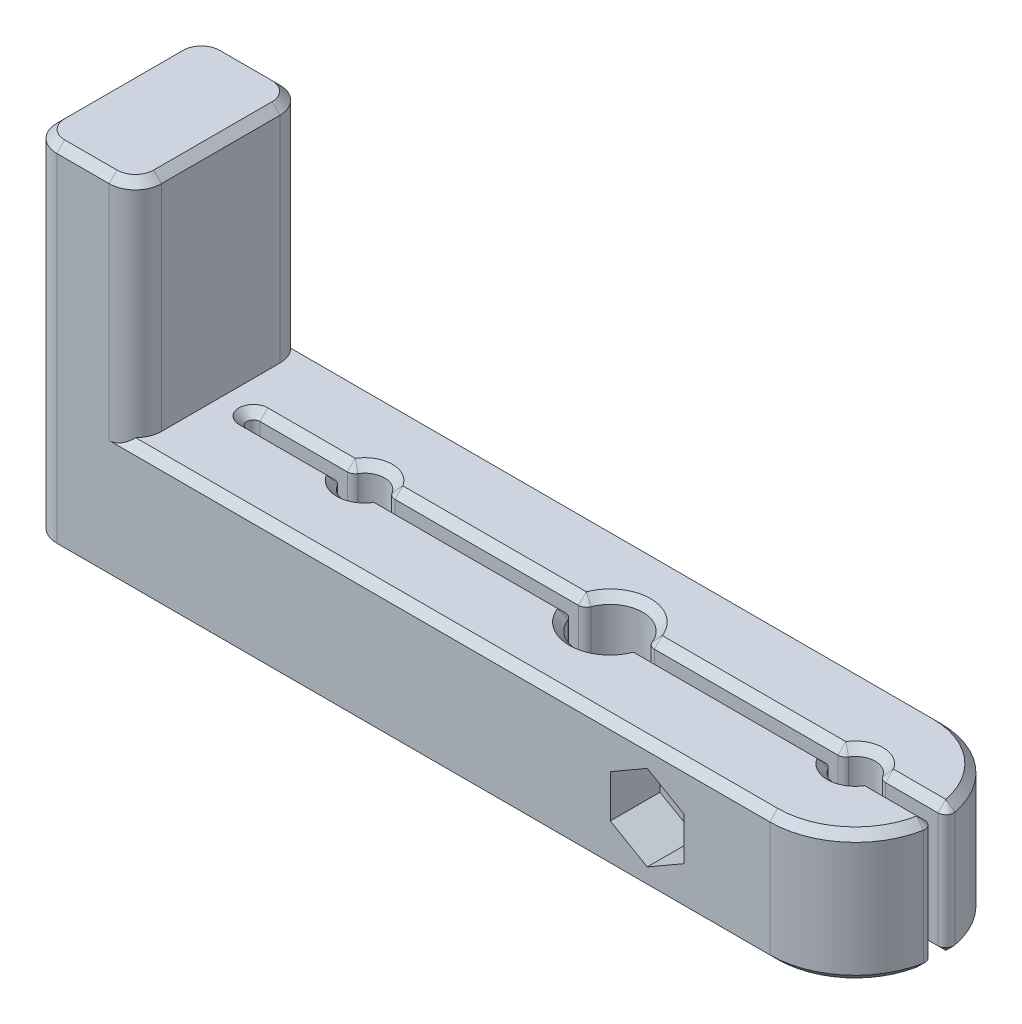
SolidWorks part; units mm, degrees
note: The reader was unsure of these and kept them because the rebuilt part matched: shared geometry of "Sketch1<4>", "Sketch3<3>".
ref_plane "Front Plane" through (0, 0, 0) normal (0, 0, 1) x (1, 0, 0)
ref_plane "Top Plane" through (0, 0, 0) normal (0, 1, 0) x (1, 0, 0)
ref_plane "Right Plane" through (0, 0, 0) normal (1, 0, 0) x (0, 0, -1)
sketch "Sketch1" plane through (0, 0, 0) normal (0, 1, 0) x (1, 0, 0)
  line L0 (0, 0) -> (-26.8494, 0) construction
  line L1 (0, 0) -> (0, 8.3452) construction
  line L2 (-18.75, 6.525) -> (18.75, 6.525)
  line L3 (-18.75, -6.525) -> (18.75, -6.525)
  line L4 (-18.75, 6.525) -> (-18.75, -6.525) construction
  line L5 (-18.75, 6.525) -> (-35.75, 6.525)
  line L6 (-37.75, 4.525) -> (-37.75, -4.525)
  line L7 (-35.75, -6.525) -> (-18.75, -6.525)
  circle A0 centre (-18.75, 0) radius 1.525
  circle A1 centre (0, 0) radius 1.5
  circle A3 centre (0, 0) radius 2.5
  circle A4 centre (18.75, 0) radius 1.525
  arc A5 (18.75, 6.525) -> (18.75, -6.525) centre (18.75, 0) cw
  arc A6 (-37.75, -4.525) -> (-35.75, -6.525) centre (-35.75, -4.525) ccw
  arc A7 (-35.75, 6.525) -> (-37.75, 4.525) centre (-35.75, 4.525) ccw
  point P12 (0, -6.525)
  point P17 (0, 6.525)
  dimension "D1" = 3
  dimension "D2" = 3.05
  dimension "D4" = 5
  dimension "D6" = 2
  dimension "D3" = 18.75
  dimension "D5" = 5
  dimension "D7" = 19
extrude "Main body" add sketch "Sketch1" along normal blind 10
extrude "Lead screw cutout" cut sketch "Sketch1<4>" along normal through all contours A3
sketch "Sketch1<4>" plane through (0, 0, 0) normal (0, 1, 0) x (1, 0, 0) same geometry as "Sketch1"
sketch "Limit switch tab sketch" plane through (0, 10, 0) normal (0, 1, 0) x (1, 0, 0)
  line L0 (-37.75, 4.525) -> (-37.75, -4.525) construction
  line L1 (-37.75, 4.525) -> (-37.75, -4.525)
  line L2 (-37.75, 0) -> (0, 0) construction
  line L3 (-33.75, 6.525) -> (-33.75, -6.525) construction
  line L4 (18.75, 6.525) -> (-35.75, 6.525) construction
  line L5 (-35.75, -6.525) -> (18.75, -6.525) construction
  line L6 (-35.75, 6.525) -> (-31.75, 6.525)
  line L7 (-35.75, -6.525) -> (-31.75, -6.525)
  line L8 (-29.75, 4.525) -> (-29.75, -4.525)
  arc A0 (-37.75, -4.525) -> (-35.75, -6.525) centre (-35.75, -4.525) ccw construction
  arc A1 (-35.75, 6.525) -> (-37.75, 4.525) centre (-35.75, 4.525) ccw construction
  arc A2 (-37.75, -4.525) -> (-35.75, -6.525) centre (-35.75, -4.525) ccw
  arc A3 (-35.75, 6.525) -> (-37.75, 4.525) centre (-35.75, 4.525) ccw
  arc A4 (-31.75, 6.525) -> (-29.75, 4.525) centre (-31.75, 4.525) cw
  arc A5 (-29.75, -4.525) -> (-31.75, -6.525) centre (-31.75, -4.525) cw
  dimension "D1" = 8
extrude "Limit switch tab" add sketch "Limit switch tab sketch" along normal blind 17
sketch "Sketch2" plane through (0, 10, 0) normal (0, 1, 0) x (1, 0, 0)
  line L0 (-27.25, 0) -> (30.9564, 0) construction
  line L1 (-27.25, 0.5) -> (27.9936, 0.5)
  line L2 (27.9936, 0.5) -> (27.9936, -0.5)
  line L3 (-27.25, -0.5) -> (27.9936, -0.5)
  line L4 (-27.75, 0) -> (-27.75, 2.9125) construction
  line L5 (-29.75, -4.525) -> (-29.75, 4.525) construction
  arc A0 (-27.25, 0.5) -> (-27.25, -0.5) centre (-27.25, 0) ccw
  point P8 (27.9936, 0)
  dimension "D1" = 1
  dimension "D2" = 2
extrude "Cut-Extrude1" cut sketch "Sketch2" against normal through all
fillet "Fillet1" radius 0.6 14 edges at (25.2558, 5, 0.5) (25.2558, 5, -0.5) (2.4495, 5, -0.5) (-2.4495, 5, -0.5) (20.1907, 5, -0.5) (17.3093, 5, -0.5) (17.3093, 5, 0.5) (20.1907, 5, 0.5) (-2.4495, 5, 0.5) (2.4495, 5, 0.5) (-20.1907, 5, 0.5) (-17.3093, 5, 0.5) (-17.3093, 5, -0.5) (-20.1907, 5, -0.5)
chamfer "Chamfer1" distance 0.6 angle 45 77 edges at (17.2265, 0, -0.5773) (18.75, 0, -1.525) (20.2735, 0, -0.5773) (22.5701, 0, -0.5) (25.034, 0, -0.7171) (22.9136, 0, -5.0239) (-8.5, 0, -6.525) (-37.1642, 0, -5.9392) (-37.75, 0, 0) (-37.1642, 0, 5.9392) (-8.5, 0, 6.525) (22.9136, 0, 5.0239) (25.034, 0, 0.7171) (22.5701, 0, 0.5) (20.2735, 0, 0.5773) (18.75, 0, 1.525) (17.2265, 0, 0.5773) (9.9151, 0, 0.5) (2.5575, 0, 0.6062) (0, 0, 2.5) (-2.5575, 0, 0.6062) (-9.9151, 0, 0.5) (-17.2265, 0, 0.5773) (-18.75, 0, 1.525) (-20.2735, 0, 0.5773) (-23.9091, 0, 0.5) (-27.75, 0, 0) (-23.9091, 0, -0.5) (-20.2735, 0, -0.5773) (-18.75, 0, -1.525) (-17.2265, 0, -0.5773) (-9.9151, 0, -0.5) (-2.5575, 0, -0.6062) (0, 0, -2.5) (2.5575, 0, -0.6062) (9.9151, 0, -0.5) (-37.75, 27, 0) (-37.1642, 27, -5.9392) (-33.75, 27, -6.525) (-30.3358, 27, -5.9392) (-29.75, 27, 0) (-30.3358, 27, 5.9392) (-33.75, 27, 6.525) (-37.1642, 27, 5.9392) (-6.5, 10, 6.525) (22.9136, 10, 5.0239) (25.034, 10, 0.7171) (22.5701, 10, 0.5) (20.2735, 10, 0.5773) (18.75, 10, 1.525) (17.2265, 10, 0.5773) (9.9151, 10, 0.5) (2.5575, 10, 0.6062) (0, 10, 2.5) (-6.5, 10, -6.525) (-2.5575, 10, 0.6062) (22.9136, 10, -5.0239) (-9.9151, 10, 0.5) (25.034, 10, -0.7171) (-17.2265, 10, 0.5773) (22.5701, 10, -0.5) (-18.75, 10, 1.525) (20.2735, 10, -0.5773) (-20.2735, 10, 0.5773) (18.75, 10, -1.525) (-23.9091, 10, 0.5) (17.2265, 10, -0.5773) (-27.75, 10, 0) (9.9151, 10, -0.5) (-23.9091, 10, -0.5) (2.5575, 10, -0.6062) (-20.2735, 10, -0.5773) (0, 10, -2.5) (-18.75, 10, -1.525) (-2.5575, 10, -0.6062) (-17.2265, 10, -0.5773) (-9.9151, 10, -0.5)
sketch "Sketch3" plane through (0, 0, 6.525) normal (0, 0, 1) x (1, 0, 0)
  line L0 (0, 0) -> (0, 10) construction
  line L1 (-30.3217, 10) -> (18.75, 10) construction
  line L2 (0, 5) -> (18.75, 5) construction
  line L4 (18.75, 9.4) -> (18.75, 0.6) construction
  line L5 (9.375, 8.262) -> (6.55, 6.631)
  line L6 (6.55, 6.631) -> (6.55, 3.369)
  line L7 (6.55, 3.369) -> (9.375, 1.738)
  line L8 (9.375, 1.738) -> (12.2, 3.369)
  line L9 (12.2, 3.369) -> (12.2, 6.631)
  line L10 (12.2, 6.631) -> (9.375, 8.262)
  line L11 (9.375, 5) -> (9.375, 8.262) construction
  line L12 (9.375, 7.0887) -> (8.3465, 6.2257)
  line L13 (9.375, 7.0887) -> (10.4035, 6.2257)
  circle A0 centre (9.375, 5) radius 2.825 construction
  arc A1 (8.3465, 6.2257) -> (10.4035, 6.2257) centre (9.375, 5) ccw
  point P20 (9.375, 5)
  dimension "D2" = 3.2
  dimension "D1" = 5.65
  dimension "D3" = 50
extrude "Cut-Extrude2" cut sketch "Sketch3" against normal blind 3.8 contours L12 A1 L13 | L9 L10 L5 L6 L7 L8 A1 L12 L13
extrude "Cut-Extrude3" cut sketch "Sketch3<3>" against normal through all contours L12 A1 L13
sketch "Sketch3<3>" plane through (0, 0, 6.525) normal (0, 0, 1) x (1, 0, 0) same geometry as "Sketch3"
sketch "Sketch4" plane through (0, 0, -6.525) normal (0, 0, -1) x (-1, 0, 0)
  line L2 (-9.375, 7.0887) -> (-8.3465, 6.2257) construction
  line L3 (-9.375, 7.0887) -> (-10.4035, 6.2257) construction
  line L6 (-9.375, 8.6878) -> (-11.1909, 7.1641)
  line L7 (-7.5591, 7.1641) -> (-9.375, 8.6878)
  circle A2 centre (-9.375, 5) radius 1.6 construction
  arc A3 (-11.1909, 7.1641) -> (-7.5591, 7.1641) centre (-9.375, 5) ccw
  arc A4 (-10.4035, 6.2257) -> (-8.3465, 6.2257) centre (-9.375, 5) ccw construction
  dimension "D1" = 2.825
extrude "Cut-Extrude4" cut sketch "Sketch4" against normal blind 3.3
equation "\"D3@Sketch1\"=37.5/2"
equation "\"D1@Sketch4\"=5.65/2"
